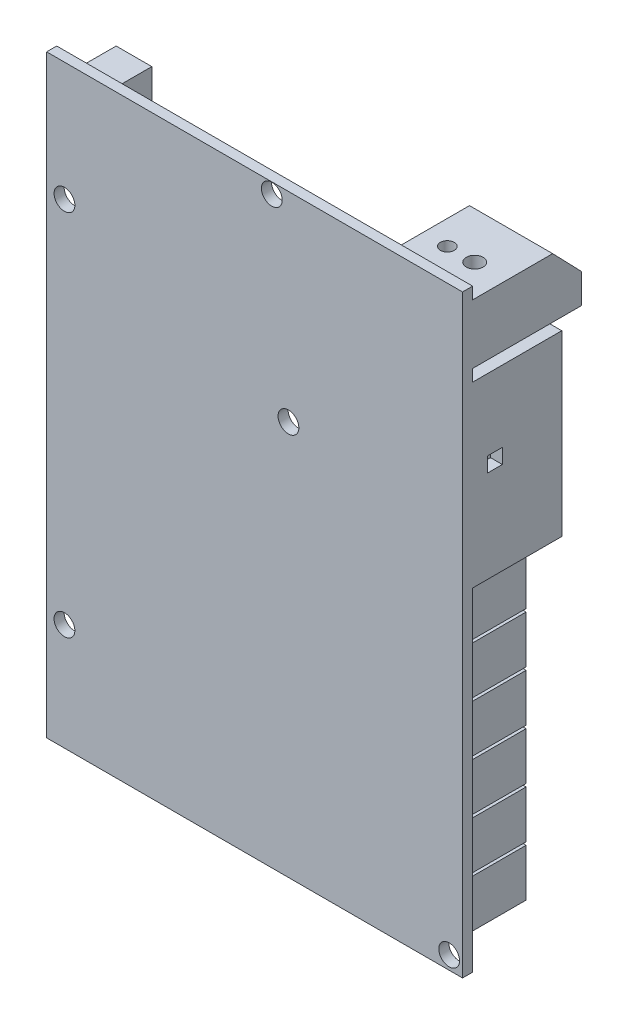
SolidWorks part; units mm, degrees
ref_plane "Ebene vorne" through (0, 0, 0) normal (0, 0, 1) x (1, 0, 0)
ref_plane "Ebene oben" through (0, 0, 0) normal (0, 1, 0) x (1, 0, 0)
ref_plane "Ebene rechts" through (0, 0, 0) normal (1, 0, 0) x (0, 0, -1)
ref_plane "Plane1" through (0, 0, -40) normal (0, 0, -1) x (-1, 0, 0)
sketch "Sketch1" plane through (0, 0, -40) normal (0, 0, -1) x (-1, 0, 0)
  line L0 (-51.2, -61.8) -> (-51.2, -161.8)
  line L1 (-51.2, -161.8) -> (18.8, -161.8)
  line L2 (18.8, -161.8) -> (18.8, -61.8)
  line L3 (18.8, -61.8) -> (-51.2, -61.8)
extrude "Boss-Extrude1" add sketch "Sketch1" against normal blind 1.7
sketch "Sketch2" plane through (0, 0, -40) normal (0, 0, -1) x (-1, 0, 0)
  line L0 (-50.2, -106.3) -> (-44.2, -106.3)
  line L1 (-44.2, -106.3) -> (-44.2, -114.3)
  line L2 (-44.2, -114.3) -> (-50.2, -114.3)
  line L3 (-50.2, -114.3) -> (-50.2, -106.3)
extrude "Boss-Extrude2" add sketch "Sketch2" along normal blind 10
sketch "Sketch3" plane through (0, 0, -50) normal (0, 0, -1) x (-1, 0, 0)
  line L0 (-44.7, -106.8) -> (-49.7, -106.8)
  line L1 (-49.7, -106.8) -> (-49.7, -113.8)
  line L2 (-49.7, -113.8) -> (-44.7, -113.8)
  line L3 (-44.7, -113.8) -> (-44.7, -106.8)
extrude "Cut-Extrude1" cut sketch "Sketch3" against normal blind 9.5
sketch "Sketch4" plane through (0, 0, -40.5) normal (0, 0, -1) x (-1, 0, 0)
  line L0 (-47.2, -111.55) -> (-47.2, -112.25)
  line L1 (-47.2, -112.25) -> (-47.7, -112.25)
  line L2 (-47.7, -112.25) -> (-47.7, -111.55)
  line L3 (-47.7, -111.55) -> (-47.2, -111.55)
extrude "Boss-Extrude3" add sketch "Sketch4" along normal blind 8.5
sketch "Sketch5" plane through (0, 0, -40.5) normal (0, 0, -1) x (-1, 0, 0)
  line L0 (-47.2, -108.35) -> (-47.2, -109.05)
  line L1 (-47.2, -109.05) -> (-47.7, -109.05)
  line L2 (-47.7, -109.05) -> (-47.7, -108.35)
  line L3 (-47.7, -108.35) -> (-47.2, -108.35)
extrude "Boss-Extrude4" add sketch "Sketch5" along normal blind 8.5
sketch "Sketch6" plane through (0, 0, -40) normal (0, 0, -1) x (-1, 0, 0)
  line L0 (11.8, -65.8) -> (17.8, -65.8)
  line L1 (17.8, -65.8) -> (17.8, -78.8)
  line L2 (17.8, -78.8) -> (11.8, -78.8)
  line L3 (11.8, -78.8) -> (11.8, -65.8)
extrude "Boss-Extrude5" add sketch "Sketch6" along normal blind 9
sketch "Sketch7" plane through (0, 0, -49) normal (0, 0, -1) x (-1, 0, 0)
  line L0 (17.3, -66.3) -> (12.3, -66.3)
  line L1 (12.3, -66.3) -> (12.3, -78.3)
  line L2 (12.3, -78.3) -> (17.3, -78.3)
  line L3 (17.3, -78.3) -> (17.3, -66.3)
extrude "Cut-Extrude2" cut sketch "Sketch7" against normal blind 8.5
sketch "Sketch8" plane through (0, 0, -40.5) normal (0, 0, -1) x (-1, 0, 0)
  line L0 (14.8, -75.55) -> (14.8, -76.25)
  line L1 (14.8, -76.25) -> (14.3, -76.25)
  line L2 (14.3, -76.25) -> (14.3, -75.55)
  line L3 (14.3, -75.55) -> (14.8, -75.55)
extrude "Boss-Extrude6" add sketch "Sketch8" along normal blind 7.5
sketch "Sketch9" plane through (0, 0, -40.5) normal (0, 0, -1) x (-1, 0, 0)
  line L0 (14.8, -68.05) -> (14.8, -68.75)
  line L1 (14.8, -68.75) -> (14.3, -68.75)
  line L2 (14.3, -68.75) -> (14.3, -68.05)
  line L3 (14.3, -68.05) -> (14.8, -68.05)
extrude "Boss-Extrude7" add sketch "Sketch9" along normal blind 7.5
sketch "Sketch10" plane through (0, 0, -40.5) normal (0, 0, -1) x (-1, 0, 0)
  line L0 (14.8, -70.55) -> (14.8, -71.25)
  line L1 (14.8, -71.25) -> (14.3, -71.25)
  line L2 (14.3, -71.25) -> (14.3, -70.55)
  line L3 (14.3, -70.55) -> (14.8, -70.55)
extrude "Boss-Extrude8" add sketch "Sketch10" along normal blind 7.5
sketch "Sketch11" plane through (0, 0, -40.5) normal (0, 0, -1) x (-1, 0, 0)
  line L0 (14.8, -73.05) -> (14.8, -73.75)
  line L1 (14.8, -73.75) -> (14.3, -73.75)
  line L2 (14.3, -73.75) -> (14.3, -73.05)
  line L3 (14.3, -73.05) -> (14.8, -73.05)
extrude "Boss-Extrude9" add sketch "Sketch11" along normal blind 7.5
sketch "Sketch12" plane through (0, 0, -40) normal (0, 0, -1) x (-1, 0, 0)
  line L0 (-50.2, -131.8) -> (-44.2, -131.8)
  line L1 (-44.2, -131.8) -> (-44.2, -139.8)
  line L2 (-44.2, -139.8) -> (-50.2, -139.8)
  line L3 (-50.2, -139.8) -> (-50.2, -131.8)
extrude "Boss-Extrude10" add sketch "Sketch12" along normal blind 10
sketch "Sketch13" plane through (0, 0, -50) normal (0, 0, -1) x (-1, 0, 0)
  line L0 (-44.7, -132.3) -> (-49.7, -132.3)
  line L1 (-49.7, -132.3) -> (-49.7, -139.3)
  line L2 (-49.7, -139.3) -> (-44.7, -139.3)
  line L3 (-44.7, -139.3) -> (-44.7, -132.3)
extrude "Cut-Extrude3" cut sketch "Sketch13" against normal blind 9.5
sketch "Sketch14" plane through (0, 0, -40.5) normal (0, 0, -1) x (-1, 0, 0)
  line L0 (-47.2, -133.85) -> (-47.2, -134.55)
  line L1 (-47.2, -134.55) -> (-47.7, -134.55)
  line L2 (-47.7, -134.55) -> (-47.7, -133.85)
  line L3 (-47.7, -133.85) -> (-47.2, -133.85)
extrude "Boss-Extrude11" add sketch "Sketch14" along normal blind 8.5
sketch "Sketch15" plane through (0, 0, -40.5) normal (0, 0, -1) x (-1, 0, 0)
  line L0 (-47.2, -137.05) -> (-47.2, -137.75)
  line L1 (-47.2, -137.75) -> (-47.7, -137.75)
  line L2 (-47.7, -137.75) -> (-47.7, -137.05)
  line L3 (-47.7, -137.05) -> (-47.2, -137.05)
extrude "Boss-Extrude12" add sketch "Sketch15" along normal blind 8.5
sketch "Sketch16" plane through (0, 0, -40) normal (0, 0, -1) x (-1, 0, 0)
  line L0 (-50.2, -123.3) -> (-44.2, -123.3)
  line L1 (-44.2, -123.3) -> (-44.2, -131.3)
  line L2 (-44.2, -131.3) -> (-50.2, -131.3)
  line L3 (-50.2, -131.3) -> (-50.2, -123.3)
extrude "Boss-Extrude13" add sketch "Sketch16" along normal blind 10
sketch "Sketch17" plane through (0, 0, -50) normal (0, 0, -1) x (-1, 0, 0)
  line L0 (-44.7, -123.8) -> (-49.7, -123.8)
  line L1 (-49.7, -123.8) -> (-49.7, -130.8)
  line L2 (-49.7, -130.8) -> (-44.7, -130.8)
  line L3 (-44.7, -130.8) -> (-44.7, -123.8)
extrude "Cut-Extrude4" cut sketch "Sketch17" against normal blind 9.5
sketch "Sketch18" plane through (0, 0, -40.5) normal (0, 0, -1) x (-1, 0, 0)
  line L0 (-47.2, -125.35) -> (-47.2, -126.05)
  line L1 (-47.2, -126.05) -> (-47.7, -126.05)
  line L2 (-47.7, -126.05) -> (-47.7, -125.35)
  line L3 (-47.7, -125.35) -> (-47.2, -125.35)
extrude "Boss-Extrude14" add sketch "Sketch18" along normal blind 8.5
sketch "Sketch19" plane through (0, 0, -40.5) normal (0, 0, -1) x (-1, 0, 0)
  line L0 (-47.2, -128.55) -> (-47.2, -129.25)
  line L1 (-47.2, -129.25) -> (-47.7, -129.25)
  line L2 (-47.7, -129.25) -> (-47.7, -128.55)
  line L3 (-47.7, -128.55) -> (-47.2, -128.55)
extrude "Boss-Extrude15" add sketch "Sketch19" along normal blind 8.5
sketch "Sketch20" plane through (0, 0, -40) normal (0, 0, -1) x (-1, 0, 0)
  line L0 (11.8, -107.8) -> (17.8, -107.8)
  line L1 (17.8, -107.8) -> (17.8, -120.8)
  line L2 (17.8, -120.8) -> (11.8, -120.8)
  line L3 (11.8, -120.8) -> (11.8, -107.8)
extrude "Boss-Extrude16" add sketch "Sketch20" along normal blind 9
sketch "Sketch21" plane through (0, 0, -49) normal (0, 0, -1) x (-1, 0, 0)
  line L0 (17.3, -108.3) -> (12.3, -108.3)
  line L1 (12.3, -108.3) -> (12.3, -120.3)
  line L2 (12.3, -120.3) -> (17.3, -120.3)
  line L3 (17.3, -120.3) -> (17.3, -108.3)
extrude "Cut-Extrude5" cut sketch "Sketch21" against normal blind 8.5
sketch "Sketch22" plane through (0, 0, -40.5) normal (0, 0, -1) x (-1, 0, 0)
  line L0 (14.8, -117.55) -> (14.8, -118.25)
  line L1 (14.8, -118.25) -> (14.3, -118.25)
  line L2 (14.3, -118.25) -> (14.3, -117.55)
  line L3 (14.3, -117.55) -> (14.8, -117.55)
extrude "Boss-Extrude17" add sketch "Sketch22" along normal blind 7.5
sketch "Sketch23" plane through (0, 0, -40.5) normal (0, 0, -1) x (-1, 0, 0)
  line L0 (14.8, -115.05) -> (14.8, -115.75)
  line L1 (14.8, -115.75) -> (14.3, -115.75)
  line L2 (14.3, -115.75) -> (14.3, -115.05)
  line L3 (14.3, -115.05) -> (14.8, -115.05)
extrude "Boss-Extrude18" add sketch "Sketch23" along normal blind 7.5
sketch "Sketch24" plane through (0, 0, -40.5) normal (0, 0, -1) x (-1, 0, 0)
  line L0 (14.8, -112.55) -> (14.8, -113.25)
  line L1 (14.8, -113.25) -> (14.3, -113.25)
  line L2 (14.3, -113.25) -> (14.3, -112.55)
  line L3 (14.3, -112.55) -> (14.8, -112.55)
extrude "Boss-Extrude19" add sketch "Sketch24" along normal blind 7.5
sketch "Sketch25" plane through (0, 0, -40.5) normal (0, 0, -1) x (-1, 0, 0)
  line L0 (14.8, -110.05) -> (14.8, -110.75)
  line L1 (14.8, -110.75) -> (14.3, -110.75)
  line L2 (14.3, -110.75) -> (14.3, -110.05)
  line L3 (14.3, -110.05) -> (14.8, -110.05)
extrude "Boss-Extrude20" add sketch "Sketch25" along normal blind 7.5
sketch "Sketch26" plane through (0, 0, -40) normal (0, 0, -1) x (-1, 0, 0)
  line L0 (-42.2, -109.3) -> (-36.2, -109.3)
  line L1 (-36.2, -109.3) -> (-36.2, -117.3)
  line L2 (-36.2, -117.3) -> (-42.2, -117.3)
  line L3 (-42.2, -117.3) -> (-42.2, -109.3)
extrude "Boss-Extrude21" add sketch "Sketch26" along normal blind 10
sketch "Sketch27" plane through (0, 0, -50) normal (0, 0, -1) x (-1, 0, 0)
  line L0 (-36.7, -109.8) -> (-41.7, -109.8)
  line L1 (-41.7, -109.8) -> (-41.7, -116.8)
  line L2 (-41.7, -116.8) -> (-36.7, -116.8)
  line L3 (-36.7, -116.8) -> (-36.7, -109.8)
extrude "Cut-Extrude6" cut sketch "Sketch27" against normal blind 9.5
sketch "Sketch28" plane through (0, 0, -40.5) normal (0, 0, -1) x (-1, 0, 0)
  line L0 (-39.2, -111.35) -> (-39.2, -112.05)
  line L1 (-39.2, -112.05) -> (-39.7, -112.05)
  line L2 (-39.7, -112.05) -> (-39.7, -111.35)
  line L3 (-39.7, -111.35) -> (-39.2, -111.35)
extrude "Boss-Extrude22" add sketch "Sketch28" along normal blind 8.5
sketch "Sketch29" plane through (0, 0, -40.5) normal (0, 0, -1) x (-1, 0, 0)
  line L0 (-39.2, -114.55) -> (-39.2, -115.25)
  line L1 (-39.2, -115.25) -> (-39.7, -115.25)
  line L2 (-39.7, -115.25) -> (-39.7, -114.55)
  line L3 (-39.7, -114.55) -> (-39.2, -114.55)
extrude "Boss-Extrude23" add sketch "Sketch29" along normal blind 8.5
sketch "Sketch30" plane through (0, 0, -40) normal (0, 0, -1) x (-1, 0, 0)
  line L0 (-50.2, -140.3) -> (-44.2, -140.3)
  line L1 (-44.2, -140.3) -> (-44.2, -148.3)
  line L2 (-44.2, -148.3) -> (-50.2, -148.3)
  line L3 (-50.2, -148.3) -> (-50.2, -140.3)
extrude "Boss-Extrude24" add sketch "Sketch30" along normal blind 10
sketch "Sketch31" plane through (0, 0, -50) normal (0, 0, -1) x (-1, 0, 0)
  line L0 (-44.7, -140.8) -> (-49.7, -140.8)
  line L1 (-49.7, -140.8) -> (-49.7, -147.8)
  line L2 (-49.7, -147.8) -> (-44.7, -147.8)
  line L3 (-44.7, -147.8) -> (-44.7, -140.8)
extrude "Cut-Extrude7" cut sketch "Sketch31" against normal blind 9.5
sketch "Sketch32" plane through (0, 0, -40.5) normal (0, 0, -1) x (-1, 0, 0)
  line L0 (-47.2, -142.35) -> (-47.2, -143.05)
  line L1 (-47.2, -143.05) -> (-47.7, -143.05)
  line L2 (-47.7, -143.05) -> (-47.7, -142.35)
  line L3 (-47.7, -142.35) -> (-47.2, -142.35)
extrude "Boss-Extrude25" add sketch "Sketch32" along normal blind 8.5
sketch "Sketch33" plane through (0, 0, -40.5) normal (0, 0, -1) x (-1, 0, 0)
  line L0 (-47.2, -145.55) -> (-47.2, -146.25)
  line L1 (-47.2, -146.25) -> (-47.7, -146.25)
  line L2 (-47.7, -146.25) -> (-47.7, -145.55)
  line L3 (-47.7, -145.55) -> (-47.2, -145.55)
extrude "Boss-Extrude26" add sketch "Sketch33" along normal blind 8.5
sketch "Sketch34" plane through (0, 0, -40) normal (0, 0, -1) x (-1, 0, 0)
  line L0 (11.8, -125.8) -> (17.8, -125.8)
  line L1 (17.8, -125.8) -> (17.8, -138.8)
  line L2 (17.8, -138.8) -> (11.8, -138.8)
  line L3 (11.8, -138.8) -> (11.8, -125.8)
extrude "Boss-Extrude27" add sketch "Sketch34" along normal blind 9
sketch "Sketch35" plane through (0, 0, -49) normal (0, 0, -1) x (-1, 0, 0)
  line L0 (17.3, -126.3) -> (12.3, -126.3)
  line L1 (12.3, -126.3) -> (12.3, -138.3)
  line L2 (12.3, -138.3) -> (17.3, -138.3)
  line L3 (17.3, -138.3) -> (17.3, -126.3)
extrude "Cut-Extrude8" cut sketch "Sketch35" against normal blind 8.5
sketch "Sketch36" plane through (0, 0, -40.5) normal (0, 0, -1) x (-1, 0, 0)
  line L0 (14.8, -128.05) -> (14.8, -128.75)
  line L1 (14.8, -128.75) -> (14.3, -128.75)
  line L2 (14.3, -128.75) -> (14.3, -128.05)
  line L3 (14.3, -128.05) -> (14.8, -128.05)
extrude "Boss-Extrude28" add sketch "Sketch36" along normal blind 7.5
sketch "Sketch37" plane through (0, 0, -40.5) normal (0, 0, -1) x (-1, 0, 0)
  line L0 (14.8, -135.55) -> (14.8, -136.25)
  line L1 (14.8, -136.25) -> (14.3, -136.25)
  line L2 (14.3, -136.25) -> (14.3, -135.55)
  line L3 (14.3, -135.55) -> (14.8, -135.55)
extrude "Boss-Extrude29" add sketch "Sketch37" along normal blind 7.5
sketch "Sketch38" plane through (0, 0, -40.5) normal (0, 0, -1) x (-1, 0, 0)
  line L0 (14.8, -133.05) -> (14.8, -133.75)
  line L1 (14.8, -133.75) -> (14.3, -133.75)
  line L2 (14.3, -133.75) -> (14.3, -133.05)
  line L3 (14.3, -133.05) -> (14.8, -133.05)
extrude "Boss-Extrude30" add sketch "Sketch38" along normal blind 7.5
sketch "Sketch39" plane through (0, 0, -40.5) normal (0, 0, -1) x (-1, 0, 0)
  line L0 (14.8, -130.55) -> (14.8, -131.25)
  line L1 (14.8, -131.25) -> (14.3, -131.25)
  line L2 (14.3, -131.25) -> (14.3, -130.55)
  line L3 (14.3, -130.55) -> (14.8, -130.55)
extrude "Boss-Extrude31" add sketch "Sketch39" along normal blind 7.5
sketch "Sketch40" plane through (0, 0, -40) normal (0, 0, -1) x (-1, 0, 0)
  line L0 (-50.2, -148.8) -> (-44.2, -148.8)
  line L1 (-44.2, -148.8) -> (-44.2, -156.8)
  line L2 (-44.2, -156.8) -> (-50.2, -156.8)
  line L3 (-50.2, -156.8) -> (-50.2, -148.8)
extrude "Boss-Extrude32" add sketch "Sketch40" along normal blind 10
sketch "Sketch41" plane through (0, 0, -50) normal (0, 0, -1) x (-1, 0, 0)
  line L0 (-44.7, -149.3) -> (-49.7, -149.3)
  line L1 (-49.7, -149.3) -> (-49.7, -156.3)
  line L2 (-49.7, -156.3) -> (-44.7, -156.3)
  line L3 (-44.7, -156.3) -> (-44.7, -149.3)
extrude "Cut-Extrude9" cut sketch "Sketch41" against normal blind 9.5
sketch "Sketch42" plane through (0, 0, -40.5) normal (0, 0, -1) x (-1, 0, 0)
  line L0 (-47.2, -154.05) -> (-47.2, -154.75)
  line L1 (-47.2, -154.75) -> (-47.7, -154.75)
  line L2 (-47.7, -154.75) -> (-47.7, -154.05)
  line L3 (-47.7, -154.05) -> (-47.2, -154.05)
extrude "Boss-Extrude33" add sketch "Sketch42" along normal blind 8.5937
sketch "Sketch43" plane through (0, 0, -40.5) normal (0, 0, -1) x (-1, 0, 0)
  line L0 (-47.2, -150.85) -> (-47.2, -151.55)
  line L1 (-47.2, -151.55) -> (-47.7, -151.55)
  line L2 (-47.7, -151.55) -> (-47.7, -150.85)
  line L3 (-47.7, -150.85) -> (-47.2, -150.85)
extrude "Boss-Extrude34" add sketch "Sketch43" along normal blind 8.5937
sketch "Sketch44" plane through (0, 0, -40) normal (0, 0, -1) x (-1, 0, 0)
  line L0 (11.8, -86.8) -> (17.8, -86.8)
  line L1 (17.8, -86.8) -> (17.8, -99.8)
  line L2 (17.8, -99.8) -> (11.8, -99.8)
  line L3 (11.8, -99.8) -> (11.8, -86.8)
extrude "Boss-Extrude35" add sketch "Sketch44" along normal blind 9
sketch "Sketch45" plane through (0, 0, -49) normal (0, 0, -1) x (-1, 0, 0)
  line L0 (17.3, -87.3) -> (12.3, -87.3)
  line L1 (12.3, -87.3) -> (12.3, -99.3)
  line L2 (12.3, -99.3) -> (17.3, -99.3)
  line L3 (17.3, -99.3) -> (17.3, -87.3)
extrude "Cut-Extrude10" cut sketch "Sketch45" against normal blind 8.5
sketch "Sketch46" plane through (0, 0, -40.5) normal (0, 0, -1) x (-1, 0, 0)
  line L0 (14.8, -96.55) -> (14.8, -97.25)
  line L1 (14.8, -97.25) -> (14.3, -97.25)
  line L2 (14.3, -97.25) -> (14.3, -96.55)
  line L3 (14.3, -96.55) -> (14.8, -96.55)
extrude "Boss-Extrude36" add sketch "Sketch46" along normal blind 7.5
sketch "Sketch47" plane through (0, 0, -40.5) normal (0, 0, -1) x (-1, 0, 0)
  line L0 (14.8, -94.05) -> (14.8, -94.75)
  line L1 (14.8, -94.75) -> (14.3, -94.75)
  line L2 (14.3, -94.75) -> (14.3, -94.05)
  line L3 (14.3, -94.05) -> (14.8, -94.05)
extrude "Boss-Extrude37" add sketch "Sketch47" along normal blind 7.5
sketch "Sketch48" plane through (0, 0, -40.5) normal (0, 0, -1) x (-1, 0, 0)
  line L0 (14.8, -89.05) -> (14.8, -89.75)
  line L1 (14.8, -89.75) -> (14.3, -89.75)
  line L2 (14.3, -89.75) -> (14.3, -89.05)
  line L3 (14.3, -89.05) -> (14.8, -89.05)
extrude "Boss-Extrude38" add sketch "Sketch48" along normal blind 7.5
sketch "Sketch49" plane through (0, 0, -40.5) normal (0, 0, -1) x (-1, 0, 0)
  line L0 (14.8, -91.55) -> (14.8, -92.25)
  line L1 (14.8, -92.25) -> (14.3, -92.25)
  line L2 (14.3, -92.25) -> (14.3, -91.55)
  line L3 (14.3, -91.55) -> (14.8, -91.55)
extrude "Boss-Extrude39" add sketch "Sketch49" along normal blind 7.5
sketch "Sketch50" plane through (0, 0, -40) normal (0, 0, -1) x (-1, 0, 0)
  line L0 (-50.2, -114.8) -> (-44.2, -114.8)
  line L1 (-44.2, -114.8) -> (-44.2, -122.8)
  line L2 (-44.2, -122.8) -> (-50.2, -122.8)
  line L3 (-50.2, -122.8) -> (-50.2, -114.8)
extrude "Boss-Extrude40" add sketch "Sketch50" along normal blind 10
sketch "Sketch51" plane through (0, 0, -50) normal (0, 0, -1) x (-1, 0, 0)
  line L0 (-44.7, -115.3) -> (-49.7, -115.3)
  line L1 (-49.7, -115.3) -> (-49.7, -122.3)
  line L2 (-49.7, -122.3) -> (-44.7, -122.3)
  line L3 (-44.7, -122.3) -> (-44.7, -115.3)
extrude "Cut-Extrude11" cut sketch "Sketch51" against normal blind 9.5
sketch "Sketch52" plane through (0, 0, -40.5) normal (0, 0, -1) x (-1, 0, 0)
  line L0 (-47.2, -116.85) -> (-47.2, -117.55)
  line L1 (-47.2, -117.55) -> (-47.7, -117.55)
  line L2 (-47.7, -117.55) -> (-47.7, -116.85)
  line L3 (-47.7, -116.85) -> (-47.2, -116.85)
extrude "Boss-Extrude41" add sketch "Sketch52" along normal blind 8.5
sketch "Sketch53" plane through (0, 0, -40.5) normal (0, 0, -1) x (-1, 0, 0)
  line L0 (-47.2, -120.05) -> (-47.2, -120.75)
  line L1 (-47.2, -120.75) -> (-47.7, -120.75)
  line L2 (-47.7, -120.75) -> (-47.7, -120.05)
  line L3 (-47.7, -120.05) -> (-47.2, -120.05)
extrude "Boss-Extrude42" add sketch "Sketch53" along normal blind 8.5
sketch "Sketch54" plane through (0, 0, -40) normal (0, 0, -1) x (-1, 0, 0)
  line L0 (-43.7, -161.8) -> (-43.7, -151.8)
  line L1 (-43.7, -151.8) -> (-23.7, -151.8)
  line L2 (-23.7, -151.8) -> (-23.7, -161.8)
  line L3 (-23.7, -161.8) -> (-43.7, -161.8)
extrude "Boss-Extrude43" add sketch "Sketch54" along normal blind 10
sketch "Sketch55" plane through (0, 0, -50) normal (0, 0, -1) x (-1, 0, 0)
  line L0 (-43.2, -152.3) -> (-43.2, -161.3)
  line L1 (-43.2, -161.3) -> (-24.2, -161.3)
  line L2 (-24.2, -161.3) -> (-24.2, -152.3)
  line L3 (-24.2, -152.3) -> (-43.2, -152.3)
extrude "Cut-Extrude12" cut sketch "Sketch55" against normal blind 9.5
sketch "Sketch56" plane through (0, 0, -40.5) normal (0, 0, -1) x (-1, 0, 0)
  line L0 (-36.7, -154.85) -> (-36.7, -155.55)
  line L1 (-36.7, -155.55) -> (-37.2, -155.55)
  line L2 (-37.2, -155.55) -> (-37.2, -154.85)
  line L3 (-37.2, -154.85) -> (-36.7, -154.85)
extrude "Boss-Extrude44" add sketch "Sketch56" along normal blind 8.5937
sketch "Sketch57" plane through (0, 0, -40.5) normal (0, 0, -1) x (-1, 0, 0)
  line L0 (-27.7, -154.85) -> (-27.7, -155.55)
  line L1 (-27.7, -155.55) -> (-28.2, -155.55)
  line L2 (-28.2, -155.55) -> (-28.2, -154.85)
  line L3 (-28.2, -154.85) -> (-27.7, -154.85)
extrude "Boss-Extrude45" add sketch "Sketch57" along normal blind 8.5937
sketch "Sketch58" plane through (0, 0, -40.5) normal (0, 0, -1) x (-1, 0, 0)
  line L0 (-27.7, -158.05) -> (-27.7, -158.75)
  line L1 (-27.7, -158.75) -> (-28.2, -158.75)
  line L2 (-28.2, -158.75) -> (-28.2, -158.05)
  line L3 (-28.2, -158.05) -> (-27.7, -158.05)
extrude "Boss-Extrude46" add sketch "Sketch58" along normal blind 8.5937
sketch "Sketch59" plane through (0, 0, -40.5) normal (0, 0, -1) x (-1, 0, 0)
  line L0 (-36.7, -158.05) -> (-36.7, -158.75)
  line L1 (-36.7, -158.75) -> (-37.2, -158.75)
  line L2 (-37.2, -158.75) -> (-37.2, -158.05)
  line L3 (-37.2, -158.05) -> (-36.7, -158.05)
extrude "Boss-Extrude47" add sketch "Sketch59" along normal blind 8.5937
sketch "Sketch60" plane through (0, 0, -40.5) normal (0, 0, -1) x (-1, 0, 0)
  line L0 (-30.7, -158.05) -> (-30.7, -158.75)
  line L1 (-30.7, -158.75) -> (-31.2, -158.75)
  line L2 (-31.2, -158.75) -> (-31.2, -158.05)
  line L3 (-31.2, -158.05) -> (-30.7, -158.05)
extrude "Boss-Extrude48" add sketch "Sketch60" along normal blind 8.5937
sketch "Sketch61" plane through (0, 0, -40.5) normal (0, 0, -1) x (-1, 0, 0)
  line L0 (-39.7, -154.85) -> (-39.7, -155.55)
  line L1 (-39.7, -155.55) -> (-40.2, -155.55)
  line L2 (-40.2, -155.55) -> (-40.2, -154.85)
  line L3 (-40.2, -154.85) -> (-39.7, -154.85)
extrude "Boss-Extrude49" add sketch "Sketch61" along normal blind 8.5937
sketch "Sketch62" plane through (0, 0, -40.5) normal (0, 0, -1) x (-1, 0, 0)
  line L0 (-33.7, -158.05) -> (-33.7, -158.75)
  line L1 (-33.7, -158.75) -> (-34.2, -158.75)
  line L2 (-34.2, -158.75) -> (-34.2, -158.05)
  line L3 (-34.2, -158.05) -> (-33.7, -158.05)
extrude "Boss-Extrude50" add sketch "Sketch62" along normal blind 8.5937
sketch "Sketch63" plane through (0, 0, -40.5) normal (0, 0, -1) x (-1, 0, 0)
  line L0 (-30.7, -154.85) -> (-30.7, -155.55)
  line L1 (-30.7, -155.55) -> (-31.2, -155.55)
  line L2 (-31.2, -155.55) -> (-31.2, -154.85)
  line L3 (-31.2, -154.85) -> (-30.7, -154.85)
extrude "Boss-Extrude51" add sketch "Sketch63" along normal blind 8.5937
sketch "Sketch64" plane through (0, 0, -40.5) normal (0, 0, -1) x (-1, 0, 0)
  line L0 (-33.7, -154.85) -> (-33.7, -155.55)
  line L1 (-33.7, -155.55) -> (-34.2, -155.55)
  line L2 (-34.2, -155.55) -> (-34.2, -154.85)
  line L3 (-34.2, -154.85) -> (-33.7, -154.85)
extrude "Boss-Extrude52" add sketch "Sketch64" along normal blind 8.5937
sketch "Sketch65" plane through (0, 0, -40.5) normal (0, 0, -1) x (-1, 0, 0)
  line L0 (-39.7, -158.05) -> (-39.7, -158.75)
  line L1 (-39.7, -158.75) -> (-40.2, -158.75)
  line L2 (-40.2, -158.75) -> (-40.2, -158.05)
  line L3 (-40.2, -158.05) -> (-39.7, -158.05)
extrude "Boss-Extrude53" add sketch "Sketch65" along normal blind 8.5937
sketch "Sketch66" plane through (0, 0, -40) normal (0, 0, -1) x (-1, 0, 0)
  line L0 (-11.5, -161.8) -> (-11.5, -151.8)
  line L1 (-11.5, -151.8) -> (-3.5, -151.8)
  line L2 (-3.5, -151.8) -> (-3.5, -161.8)
  line L3 (-3.5, -161.8) -> (-11.5, -161.8)
extrude "Boss-Extrude54" add sketch "Sketch66" along normal blind 4.1
sketch "Sketch67" plane through (0, -161.8, 0) normal (0, -1, 0) x (1, 0, 0)
  line L0 (11, -43.1) -> (11, -40.5)
  line L1 (11, -40.5) -> (4, -40.5)
  line L2 (4, -40.5) -> (4, -43.1)
  line L3 (4, -43.1) -> (11, -43.1)
extrude "Cut-Extrude13" cut sketch "Sketch67" against normal blind 9.5
sketch "Sketch68" plane through (0, 0, -40) normal (0, 0, -1) x (-1, 0, 0)
  line L0 (1.3, -161.8) -> (1.3, -146.8)
  line L1 (1.3, -146.8) -> (16.3, -146.8)
  line L2 (16.3, -146.8) -> (16.3, -161.8)
  line L3 (16.3, -161.8) -> (1.3, -161.8)
extrude "Boss-Extrude55" add sketch "Sketch68" along normal blind 1.9
sketch "Sketch69" plane through (0, -161.8, 0) normal (0, -1, 0) x (1, 0, 0)
  line L0 (-1.8, -41) -> (-1.8, -40.5)
  line L1 (-1.8, -40.5) -> (-15.8, -40.5)
  line L2 (-15.8, -40.5) -> (-15.8, -41)
  line L3 (-15.8, -41) -> (-1.8, -41)
extrude "Cut-Extrude14" cut sketch "Sketch69" against normal blind 14.5
ref_plane "Plane2" through (51.2, 0, 0) normal (1, 0, 0) x (0, 0, -1)
sketch "Sketch70" plane through (51.2, 0, 0) normal (1, 0, 0) x (0, 0, -1)
  line L0 (40, -73.8) -> (58.3, -73.8)
  line L1 (58.3, -73.8) -> (58.3, -68.8)
  line L2 (58.3, -68.8) -> (53.4716, -63.8)
  line L3 (53.4716, -63.8) -> (40, -63.8)
  line L4 (40, -63.8) -> (40, -73.8)
extrude "Boss-Extrude56" add sketch "Sketch70" against normal blind 14
sketch "Sketch71" plane through (0, 0, -40) normal (0, 0, -1) x (-1, 0, 0)
  line L0 (-51.2, -105.8) -> (-51.2, -75.8)
  line L1 (-51.2, -75.8) -> (-41.2, -75.8)
  line L2 (-41.2, -75.8) -> (-41.2, -105.8)
  line L3 (-41.2, -105.8) -> (-51.2, -105.8)
extrude "Boss-Extrude57" add sketch "Sketch71" along normal blind 15
sketch "Sketch72" plane through (51.2, 0, 0) normal (1, 0, 0) x (0, 0, -1)
  line L0 (42.5, -90.3) -> (45, -90.3)
  line L1 (45, -90.3) -> (45, -87.8)
  line L2 (45, -87.8) -> (42.5, -87.8)
  line L3 (42.5, -87.8) -> (42.5, -90.3)
extrude "Cut-Extrude15" cut sketch "Sketch72" against normal blind 2
hole_wizard "Ø3.5 (3.5) Diameter Hole1" positions "Sketch74" profile "Sketch73" hole size "Ø3.5" standard "ANSI Metric"
sketch "Sketch74" plane through (0, 0, -40) normal (0, 0, -1) x (-1, 0, 0)
  point P0 (-48.95, -159.55)
  point P1 (15.8, -81.8)
  point P2 (15.8, -143.8)
  point P3 (-21.9, -95.4)
  point P4 (-19.1, -63.6)
  point P5 (0, 0)
sketch "Sketch73" plane through (48.95, -159.55, -40) normal (1, 0, 0) x (0, 1, 0)
  line L0 (0, 0) -> (0, 1.7)
  line L1 (0, 1.7) -> (1.75, 1.7)
  line L2 (1.75, 1.7) -> (1.75, 0)
  line L5 (1.75, 0) -> (0, 0)
  line L11 (0, -6.35) -> (0, 107.95) construction
  dimension "Thru Hole Dia." = 3.5
  dimension "Thru Hole Depth" = 1.7
hole_wizard "M2 Clearance Hole1" positions "Sketch76" profile "Sketch75" hole size "M2" standard "ANSI Metric"
sketch "Sketch76" plane through (0, -63.8, 0) normal (0, 1, 0) x (1, 0, 0)
  point P0 (41.271, 45.6652)
sketch "Sketch75" plane through (41.271, -63.8, -45.6652) normal (1, 0, 0) x (0, 0, 1)
  line L0 (0, 0) -> (0, 5)
  line L1 (0, 5) -> (1.1739, 5)
  line L2 (1.1739, 5) -> (1.1739, 0)
  line L5 (1.1739, 0) -> (0, 0)
  line L10 (0, 5) -> (-1.1739, 5) construction
  line L11 (0, -6.35) -> (0, 107.95) construction
  dimension "Hole Dia." = 2.3478
  dimension "Hole Depth" = 5
  dimension "Drill Angle" = 180
hole_wizard "M2.5 Clearance Hole1" positions "Sketch78" profile "Sketch77" hole size "M2.5" standard "ANSI Metric"
sketch "Sketch78" plane through (0, -63.8, 0) normal (0, 1, 0) x (1, 0, 0)
  point P0 (45.8827, 45.6652)
sketch "Sketch77" plane through (45.8827, -63.8, -45.6652) normal (1, 0, 0) x (0, 0, 1)
  line L0 (0, 0) -> (0, 5)
  line L1 (0, 5) -> (1.4254, 5)
  line L2 (1.4254, 5) -> (1.4254, 0)
  line L5 (1.4254, 0) -> (0, 0)
  line L10 (0, 5) -> (-1.4254, 5) construction
  line L11 (0, -6.35) -> (0, 107.95) construction
  dimension "Hole Dia." = 2.8509
  dimension "Hole Depth" = 5
  dimension "Drill Angle" = 180
